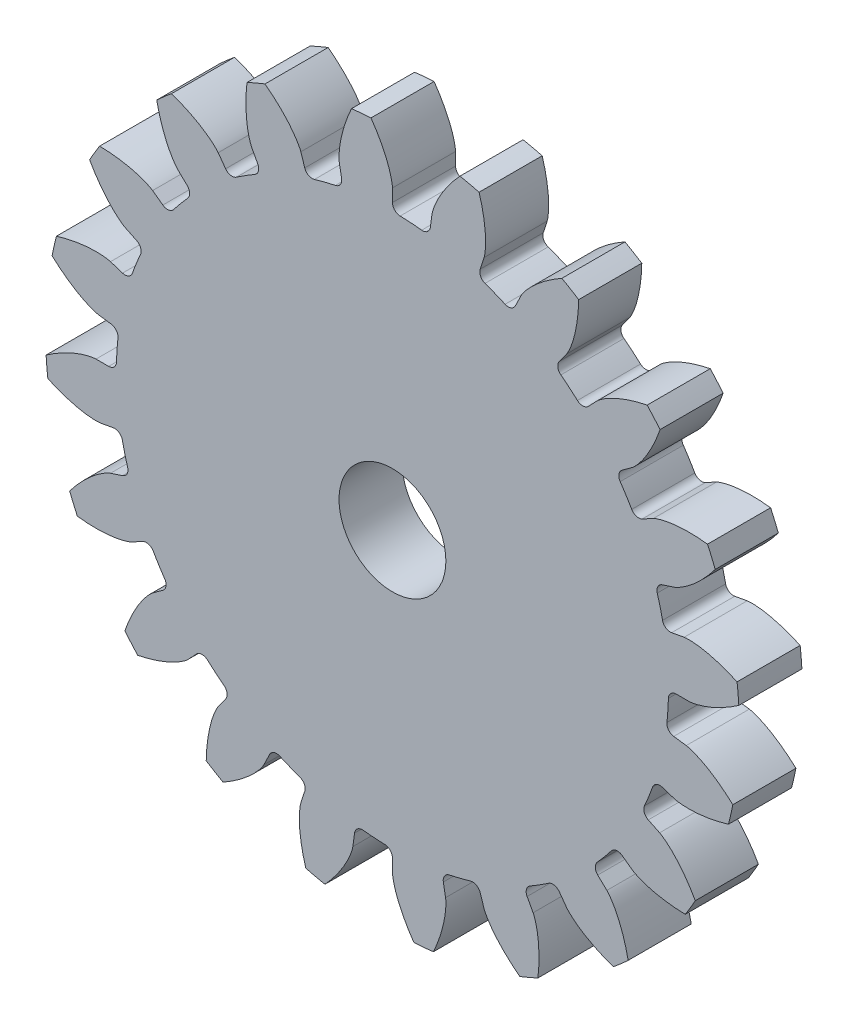
SolidWorks part; units mm, degrees
material "Acrylic (Medium-high impact)"
ref_plane "Front Plane" through (0, 0, 0) normal (0, 0, 1) x (1, 0, 0)
ref_plane "Top Plane" through (0, 0, 0) normal (0, 1, 0) x (1, 0, 0)
ref_plane "Right Plane" through (0, 0, 0) normal (1, 0, 0) x (0, 0, -1)
sketch "Sketch1" plane through (0, 0, 0) normal (0, 0, 1) x (1, 0, 0)
  line L0 (14.0954, 0) -> (13.125, 0)
  line L1 (16.4331, 1.4848) -> (-16.4331, -1.4848)
  line L2 (0, 0) -> (14.9983, 0.2236) construction
  circle A0 centre (0, 0) radius 14.0954 construction
  circle A1 centre (0, 0) radius 16.5
  circle A2 centre (0, 0) radius 13.125
  circle A3 centre (0, 0) radius 15 construction
  spline S0 degree 4 poles (14.0954, 0) (14.1058, 0.0002) (14.135, 0.0015) (14.1901, 0.0067) (14.2796, 0.0189) (14.393, 0.04) (14.5385, 0.0738) (14.7082, 0.1216) (14.8927, 0.1826) (15.0909, 0.258) (15.2861, 0.341) (15.4783, 0.4311) (15.6673, 0.5274) (15.8931, 0.6515) (16.1593, 0.8107) (16.4633, 1.0115) (16.799, 1.2565) (17.1307, 1.524) (17.4482, 1.8017) (17.758, 2.0982) (18.0498, 2.3963) (18.3408, 2.7214) (18.6032, 3.0295) (18.8829, 3.3909) (19.1045, 3.6874) (19.381, 4.0951) (19.5394, 4.3407) (19.7191, 4.6335) (19.7959, 4.7664) (19.8433, 4.8482) knots 0 0 0 0 0 0.005377 0.015084 0.028532 0.04661 0.064855 0.092111 0.119476 0.146842 0.174209 0.201575 0.228941 0.256307 0.307035 0.361767 0.4165 0.471232 0.525964 0.580697 0.635429 0.690161 0.744894 0.799626 0.854358 0.909091 0.954545 1 1 1 1 1 construction
  spline S1 degree 4 poles (14.0954, 0) (14.1058, 0.0002) (14.135, 0.0015) (14.1901, 0.0067) (14.2796, 0.0189) (14.393, 0.04) (14.5385, 0.0738) (14.7082, 0.1216) (14.8927, 0.1826) (15.0909, 0.258) (15.2861, 0.341) (15.4783, 0.4311) (15.6673, 0.5274) (15.8931, 0.6515) (16.1593, 0.8107) (16.4633, 1.0115) (16.799, 1.2565) (17.1307, 1.524) (17.4482, 1.8017) (17.758, 2.0982) (18.0498, 2.3963) (18.3408, 2.7214) (18.6032, 3.0295) (18.8829, 3.3909) (19.1045, 3.6874) (19.321, 4.0067) (19.4245, 4.1639) (19.4766, 4.2451) knots 0 0 0 0 0 0.005377 0.015084 0.028532 0.04661 0.064855 0.092111 0.119476 0.146842 0.174209 0.201575 0.228941 0.256307 0.307035 0.361767 0.4165 0.471232 0.525964 0.580697 0.635429 0.690161 0.744894 0.799626 0.854358 0.909091 0.909091 0.909091 0.909091 0.909091
  dimension "D1" = 28.1908
  dimension "D2" = 33
  dimension "D3" = 26.25
  dimension "D5" = 30
  dimension "D4" = 4.309
extrude "Boss-Extrude3" add sketch "Sketch1" along normal blind 3 contours L1 A2 | A2 L1 | L0 S1 A1 L1 A2
mirror "Mirror2" about plane through (0, 0, 3) normal (0.09, -0.9959, 0) of "Boss-Extrude3"
fillet "Fillet1" radius 0.375 2 edges at (12.9124, 2.3526, 1.5) (13.125, 0, 1.5)
pattern_circular "CirPattern8" count 20 over 360 about axis through (0, 0, 3) along (0, 0, -1) of "Boss-Extrude3", "Mirror2", "Fillet1"
sketch "Sketch3" plane through (0, 0, 3) normal (0, 0, 1) x (1, 0, 0)
  circle A0 centre (0, 0) radius 2.54
  dimension "D1" = 5.08
extrude "Cut-Extrude2" cut sketch "Sketch3" against normal through all
equation "\"d\"= 30mm'Pitch diameter"
equation "\"N\"= 20'Number of teeth"
equation "\"bl\"= 0.1mm'Backlash"
equation "\"pa\"= 20deg'Pressure angle (deg)"
equation "\"pc\"= ( 3.1415 * \"d\" ) / \"N\"\t'Circular pitch"
equation "\"m\"= \"d\" / \"N\"\t\t\t'module"
equation "\"P\"= \"N\" / \"d\"\t\t\t'Diametral pitch"
equation "\"a\"= 1/\"P\"\t\t\t'Addendum distance"
equation "\"b\"= 1.25 / \"P\"'Dedendum distance"
equation "\"rb\"= (\"d\"/2)*cos(\"pa\")\t\t'base circle radius"
equation "\"cp\"= 3.1415/\"P\"\t\t'Circular pitch"
equation "\"t\"= ( \"cp\" / 2 ) - \"bl\"'tooth tickness"
equation "\"c\"=\"b\"-\"a\"\t\t\t'Clearance"
equation "\"facewidth\"= 3mm'face width"
equation "\"rbd\"= \"rb\" * 2'base circle diameter"
equation "\"D1@Sketch1\"=\"rbd\""
equation "\"D2@Sketch1\"= \"d\" + (\"a\" * 2)"
equation "\"D3@Sketch1\" = \"ded\""
equation "\"D4@Sketch1\"= ((\"t\" /2) / (\"d\"/2)) * (180/3.1415)"
equation "\"D1@Boss-Extrude3\"=\"facewidth\""
equation "\"D1@Fillet1\"=\"c\""
equation "\"D1@CirPattern8\"=\"N\""
equation "\"D5@Sketch1\"=\"d\""
equation "\"ded1\"= \"d\" - 2 * ( ( ( \"d\" / 2 ) - \"rb\" ) + ( 0.5 * ( 1.25 / \"P\" ) ) )"
equation "\"ded2\"= \"d\" - ( \"b\" * 2 )"
equation "\"ded\"= IIF ( \"rb\" < ( \"ded2\" / 2 ) , \"ded1\" , \"ded2\" )"
equation "\"shaftdia\" = 0.2in"
equation "\"D1@Sketch3\"=\"shaftdia\""
